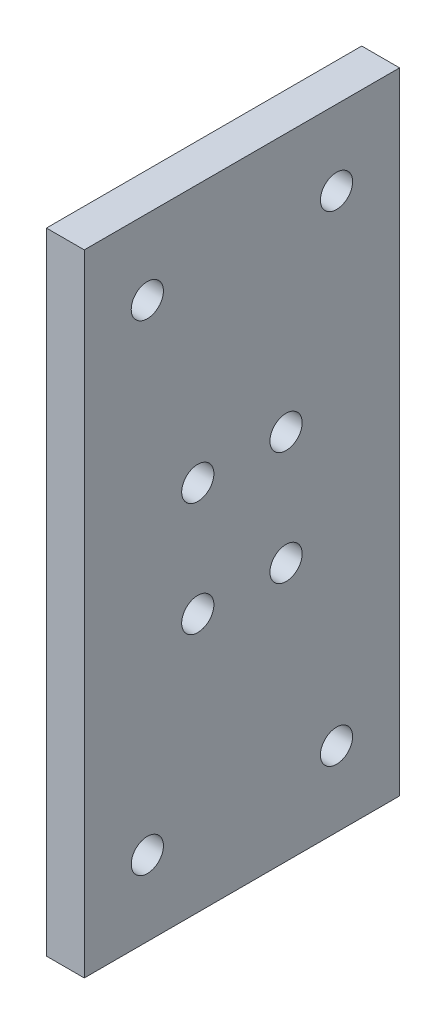
SolidWorks part; units mm, degrees
ref_plane "Front Plane" through (0, 0, 0) normal (1, 0, 0) x (0, 1, 0)
ref_plane "Top Plane" through (0, 0, 0) normal (0, 0, 1) x (0, 1, 0)
ref_plane "Right Plane" through (0, 0, 0) normal (0, 1, 0) x (-1, 0, 0)
sketch "Sketch1" plane through (0, 0, 0) normal (1, 0, 0) x (0, 1, 0)
  line L0 (0, 25) -> (0, -25) construction
  line L1 (-50, -25) -> (50, -25)
  line L2 (-50, -25) -> (-50, 25)
  line L3 (-50, 25) -> (50, 25)
  line L4 (50, -25) -> (50, 25)
  line L5 (-50, -25) -> (50, 25) construction
  line L6 (-50, 25) -> (50, -25) construction
  line L8 (-9, -7) -> (9, -7) construction
  line L9 (-9, -7) -> (-9, 7) construction
  line L10 (-9, 7) -> (9, 7) construction
  line L11 (9, -7) -> (9, 7) construction
  line L12 (-9, -7) -> (9, 7) construction
  line L13 (-9, 7) -> (9, -7) construction
  line L14 (-38.1, -15) -> (38.1, -15) construction
  line L15 (-38.1, -15) -> (-38.1, 15) construction
  line L16 (-38.1, 15) -> (38.1, 15) construction
  line L17 (38.1, -15) -> (38.1, 15) construction
  line L18 (-38.1, -15) -> (38.1, 15) construction
  line L19 (-38.1, 15) -> (38.1, -15) construction
  circle A0 centre (-9, 7) radius 2.555
  circle A1 centre (-9, -7) radius 2.555
  circle A2 centre (9, -7) radius 2.555
  circle A3 centre (9, 7) radius 2.555
  circle A4 centre (-38.1, 15) radius 2.555
  circle A5 centre (-38.1, -15) radius 2.555
  circle A6 centre (38.1, 15) radius 2.555
  circle A7 centre (38.1, -15) radius 2.555
  point P0 (0, 0)
  point P8 (0, 0)
  point P17 (0, 0)
  dimension "D5" = 5.11
  dimension "D6" = 5.11
  dimension "D9" = 5.11
  dimension "D10" = 5.11
  dimension "D1" = 14
  dimension "D2" = 18
  dimension "D3" = 100
  dimension "D4" = 50
  dimension "D7" = 76.2
  dimension "D8" = 30
extrude "Boss-Extrude1" add sketch "Sketch1" along normal blind 6
